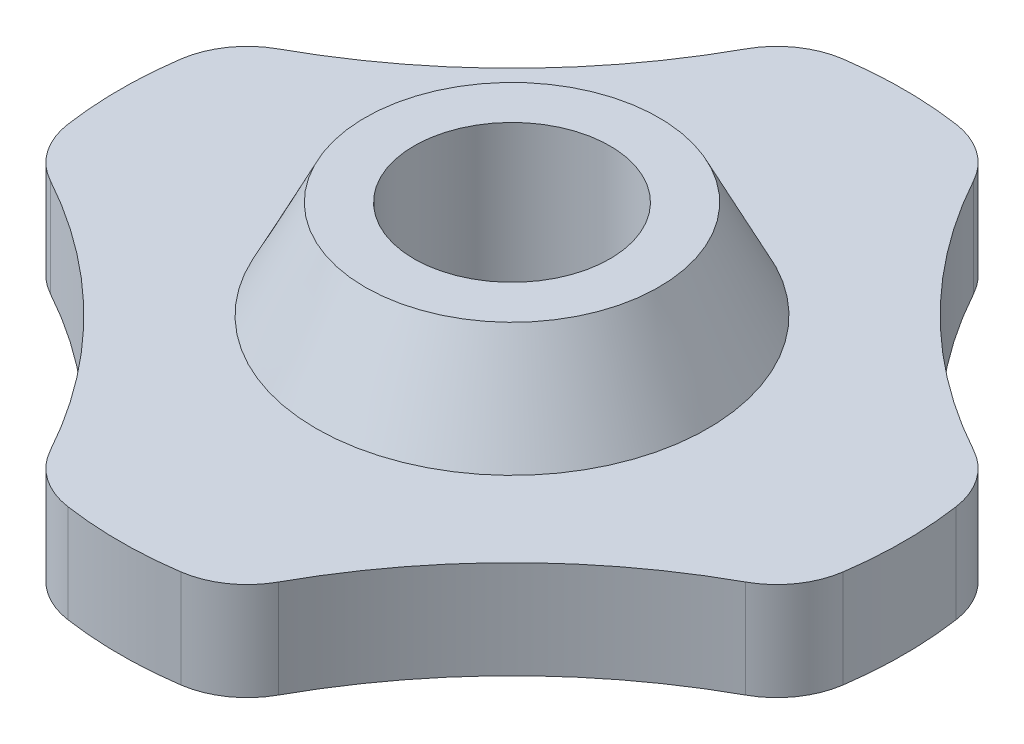
SolidWorks part; units mm, degrees
material "ABS PC"
ref_plane "Front Plane" through (0, 0, 0) normal (0, 0, 1) x (1, 0, 0)
ref_plane "Top Plane" through (0, 0, 0) normal (0, 1, 0) x (1, 0, 0)
ref_plane "Right Plane" through (0, 0, 0) normal (1, 0, 0) x (0, 0, -1)
sketch "Sketch1" plane through (0, 0, 0) normal (0, 1, 0) x (1, 0, 0)
  line L0 (-3.175, 12.2967) -> (-3.175, 5.4993)
  line L1 (3.175, 12.2967) -> (3.175, 5.4993)
  line L2 (0, 0) -> (0, 12.7) construction
  line L3 (12.2967, 3.175) -> (5.4993, 3.175)
  line L4 (12.2967, -3.175) -> (5.4993, -3.175)
  line L5 (3.175, -12.2967) -> (3.175, -5.4993)
  line L6 (-3.175, -12.2967) -> (-3.175, -5.4993)
  line L7 (-12.2967, -3.175) -> (-5.4993, -3.175)
  line L8 (-12.2967, 3.175) -> (-5.4993, 3.175)
  circle A0 centre (0, 0) radius 6.35
  circle A1 centre (0, 0) radius 3.175
  circle A2 centre (0, 0) radius 12.7
  arc A3 (-3.175, 12.2967) -> (-12.2967, 3.175) centre (-20.4106, 20.4106) cw
  arc A4 (12.2967, 3.175) -> (3.175, 12.2967) centre (20.4106, 20.4106) cw
  arc A5 (3.175, -12.2967) -> (12.2967, -3.175) centre (20.4106, -20.4106) cw
  arc A6 (-12.2967, -3.175) -> (-3.175, -12.2967) centre (-20.4106, -20.4106) cw
  point P25 (0, 0)
  point P36 (0, 0)
  dimension "D1" = 12.7
  dimension "D2" = 6.35
  dimension "D3" = 25.4
  dimension "D7" = 19.05
  dimension "D4" = 6.35
  dimension "D5" = 3.175
  dimension "D6" = 4
  dimension "D8" = 4
extrude "Boss-Extrude1" add sketch "Sketch1" along normal blind 3.175 contours L8 A2 L7 A0 | A0 L2 A2 L0 | L2 A0 L1 A2 | A1 A0 | L4 A2 L3 A0 | L6 A2 L5 A0 | L5 A2 L4 A0 | L3 A2 L1 A0 | L7 A2 L6 A0 | L0 A2 L8 A0 region at (-1.6053, 0, -9.3167) region at (-6.0514, 0, -6.0514) region at (-1.597, 0, -5.9601) region at (1.6053, 0, -9.3167) region at (-9.3167, 0, 0) region at (6.0514, 0, -6.0514) region at (-6.0514, 0, 6.0514) region at (9.3167, 0, 0) region at (0, 0, 9.3167) region at (6.0514, 0, 6.0514)
extrude "Boss-Extrude2" add sketch "Sketch1<3>" along normal blind 6.35 contours A1 A0 region at (0, 0, -6.1704)
sketch "Sketch1<3>" plane through (0, 0, 0) normal (0, 1, 0) x (1, 0, 0) same geometry as "Sketch1"
fillet "Fillet1" radius 2.54 8 edges at (12.2967, 1.5875, -3.175) (12.2967, 1.5875, 3.175) (3.175, 1.5875, 12.2967) (-3.175, 1.5875, 12.2967) (-12.2967, 1.5875, 3.175) (-12.2967, 1.5875, -3.175) (3.175, 1.5875, -12.2967) (-3.175, 1.5875, -12.2967)
chamfer "Chamfer2" distance 3.175 distance2 1.5875 1 edges at (0, 6.35, 6.35) first distance on face at (0, 3.175, 6.35)
move or copy body "Body-Move/Copy1" [suppressed] bodies to move or copy 102 parameters "D1"=0, "D2"=0, "D3"=0
move or copy body "Body-Move/Copy2" [suppressed] bodies to move or copy 103 parameters "D1"=0, "D2"=0, "D3"=0
move or copy body "Body-Move/Copy3" [suppressed] bodies to move or copy 104 parameters "D1"=0, "D2"=0, "D3"=0
move or copy body "Body-Move/Copy4" [suppressed] bodies to move or copy 105 parameters "D1"=0, "D2"=0, "D3"=0
move or copy body "Body-Move/Copy5" [suppressed] bodies to move or copy 106 parameters "D1"=0, "D2"=0, "D3"=0
move or copy body "Body-Move/Copy6" [suppressed] bodies to move or copy 107 parameters "D1"=0, "D2"=0, "D3"=0
move or copy body "Body-Move/Copy7" [suppressed] bodies to move or copy 108 parameters "D1"=0, "D2"=0, "D3"=0
move or copy body "Body-Move/Copy8" [suppressed] bodies to move or copy 109 parameters "D1"=0, "D2"=0, "D3"=0
move or copy body "Body-Move/Copy9" [suppressed] bodies to move or copy 110 parameters "D1"=0, "D2"=0, "D3"=0
move or copy body "Body-Move/Copy10" [suppressed] bodies to move or copy 111 parameters "D1"=0, "D2"=0, "D3"=0
move or copy body "Body-Move/Copy11" [suppressed] bodies to move or copy 112 parameters "D1"=0, "D2"=0, "D3"=0
move or copy body "Body-Move/Copy12" [suppressed] bodies to move or copy 113 parameters "D1"=0, "D2"=0, "D3"=0
move or copy body "Body-Move/Copy13" [suppressed] bodies to move or copy 114 parameters "D1"=0, "D2"=0, "D3"=0
move or copy body "Body-Move/Copy14" [suppressed] bodies to move or copy 115 parameters "D1"=0, "D2"=0, "D3"=0
equation "\".25n\"=0.15"
